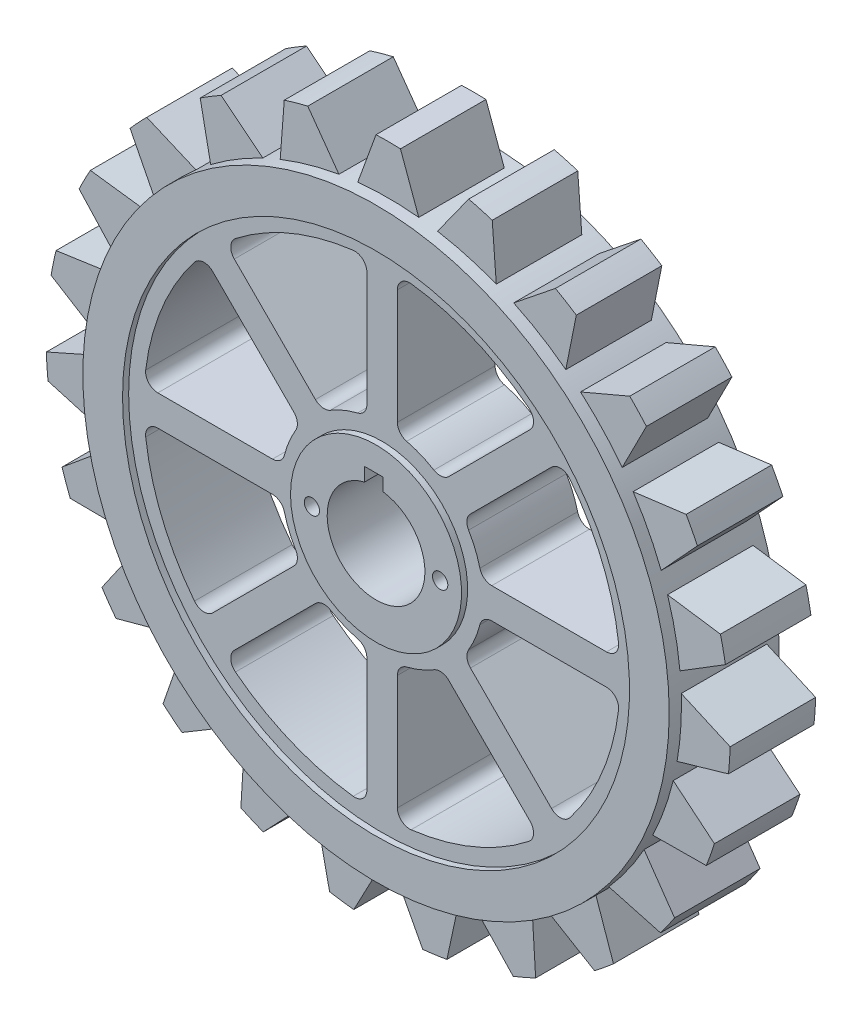
SolidWorks part; units mm, degrees
material "1060 Alloy"
ref_plane "Front Plane" through (0, 0, 0) normal (0, 0, 1) x (1, 0, 0)
ref_plane "Top Plane" through (0, 0, 0) normal (0, 1, 0) x (1, 0, 0)
ref_plane "Right Plane" through (0, 0, 0) normal (1, 0, 0) x (0, 0, -1)
sketch "Sketch2" plane through (0, 0, 0) normal (0, 0, 1) x (1, 0, 0)
  circle A0 centre (0, 0) radius 48
  dimension "D1" = 96
extrude "Boss-Extrude1" add sketch "Sketch2" along normal mid plane 18
sketch "Sketch3" plane through (0, 0, 9) normal (0, 0, 1) x (1, 0, 0)
  line L0 (0, 0) -> (0, 8) construction
  line L1 (-1.8827, 7.7753) -> (-1.8827, 10)
  line L2 (1.1173, 10) -> (-1.8827, 10)
  line L3 (1.1173, 7.9216) -> (1.1173, 10)
  line L7 (7.675, -2.2572) -> (9.6016, -3.3695)
  line L8 (8.1016, -5.9676) -> (9.6016, -3.3695)
  line L9 (6.3017, -4.9284) -> (8.1016, -5.9676)
  line L13 (-5.7922, -5.5181) -> (-7.7189, -6.6305)
  line L14 (-9.2189, -4.0324) -> (-7.7189, -6.6305)
  line L15 (-7.4189, -2.9932) -> (-9.2189, -4.0324)
  line L19 (0, 0) -> (1.1173, 7.9216) construction
  line L20 (0, 0) -> (7.4189, 2.9932) construction
  line L21 (-6.3017, 4.9284) -> (-8.1016, 5.9676) [skipped]
  line L22 (-7.675, 2.2572) -> (-9.6016, 3.3695) [skipped]
  line L23 (-8.1016, 5.9676) -> (-9.6016, 3.3695) [skipped]
  line L24 (-1.1173, -7.9216) -> (-1.1173, -10) [skipped]
  line L25 (1.8827, -7.7753) -> (1.8827, -10) [skipped]
  line L26 (-1.1173, -10) -> (1.8827, -10) [skipped]
  line L27 (7.4189, 2.9932) -> (9.2189, 4.0324) [skipped]
  line L28 (5.7922, 5.5181) -> (7.7189, 6.6305) [skipped]
  line L29 (9.2189, 4.0324) -> (7.7189, 6.6305) [skipped]
  circle A0 centre (0, 0) radius 8
  circle A1 centre (0, 0) radius 8
  circle A2 centre (0, 0) radius 8
  circle A3 centre (0, 0) radius 8
  circle A4 centre (0, 0) radius 8
  circle A5 centre (0, 0) radius 8
  dimension "D1" = 16
  dimension "D2" = 3
  dimension "D3" = 6
  dimension "10" = 10
  dimension "D4" = 60
  dimension "D5" = 8
extrude "Cut-Extrude1" cut sketch "Sketch3" against normal through all contours A0 | A0 L3 L2 L1 region at (-0.4004, 8.9709, 9) region at (0, 0, 9)
sketch "Sketch7" plane through (0, 0, -9) normal (0, 0, -1) x (-1, 0, 0)
  circle A0 centre (0, 0) radius 14
  circle A1 centre (0, 0) radius 41.5
  circle A2 centre (0, 0) radius 48 construction
  dimension "D1" = 6.5
  dimension "28" = 28
extrude "Cut-Extrude3" cut sketch "Sketch7" against normal blind 1
mirror "Mirror2" about plane through (0, 0, 0) normal (0, 0, 1) of "Cut-Extrude3"
sketch "Sketch8" plane through (0, 0, -8) normal (0, 0, -1) x (-1, 0, 0)
  line L0 (0, 0) -> (0, 41.5) construction
  line L1 (0, 0) -> (29.3449, 29.3449) construction
  line L2 (2.5, 38.9198) -> (2.5, 16.3095)
  line L4 (25.7527, 29.2882) -> (9.7648, 13.3003)
  circle A0 centre (0, 0) radius 41.5 construction
  circle A1 centre (0, 0) radius 41.5 construction
  circle A2 centre (0, 0) radius 16.5
  circle A3 centre (0, 0) radius 14 construction
  circle A4 centre (0, 0) radius 39
  dimension "D2" = 2.5
  dimension "D1" = 2.5
  dimension "2.5" = 2.5
  dimension "D3" = 2.5
extrude "Cut-Extrude4" cut sketch "Sketch8" against normal through all contours L4 A4 L2 A2 region at (-11.1952, 27.0275, -8)
fillet "Fillet1" radius 2 4 edges at (-2.5, 38.9198, 0) (-25.7527, 29.2882, 0) (-9.7648, 13.3003, 0) (-2.5, 16.3095, 0)
pattern_circular "CirPattern2" count 8 over 360 about axis through (0, 0, -9) along (0, 0, 1) of "Fillet1", "Cut-Extrude4"
sketch "Sketch9" plane through (0, 0, 0) normal (0, 0, 1) x (1, 0, 0)
  line L0 (0, 0) -> (0, 48) construction
  line L1 (-2, 55.9643) -> (-4.9936, 47.7395)
  line L2 (2, 55.9643) -> (4.9936, 47.7395)
  circle A0 centre (0, 0) radius 48 construction
  arc A1 (2, 55.9643) -> (-2, 55.9643) centre (0, 0) ccw
  arc A2 (4.9936, 47.7395) -> (-4.9936, 47.7395) centre (0, 0) ccw
  dimension "D1" = 8
  dimension "D2" = 40
  dimension "D3" = 4
extrude "Boss-Extrude2" add sketch "Sketch9" along normal mid plane 14
pattern_circular "CirPattern3" count 23 over 360 about axis through (0, 0, -9) along (0, 0, 1) of "Boss-Extrude2"
sketch "Sketch10" plane through (0, 0, 0) normal (0, 0, 1) x (1, 0, 0)
  line L0 (0, 8) -> (0, -8)
  line L1 (0, -8) -> (0, 0)
  line L2 (0, 0) -> (8, 0)
  line L3 (8, 0) -> (-8, 0)
  arc A0 (-1.8827, 7.7753) -> (1.1173, 7.9216) centre (0, 0) ccw construction
  circle A1 centre (-10.5, 0) radius 1.25
  circle A2 centre (10.5, 0) radius 1.25
  point P8 (0, 0)
  dimension "D1" = 2.5
  dimension "D2" = 2.5
extrude "Cut-Extrude5" cut sketch "Sketch10" against normal through all both and the other way through all contours A1 | A2 region at (-10.5, 0, 0) region at (10.5, 0, 0)
